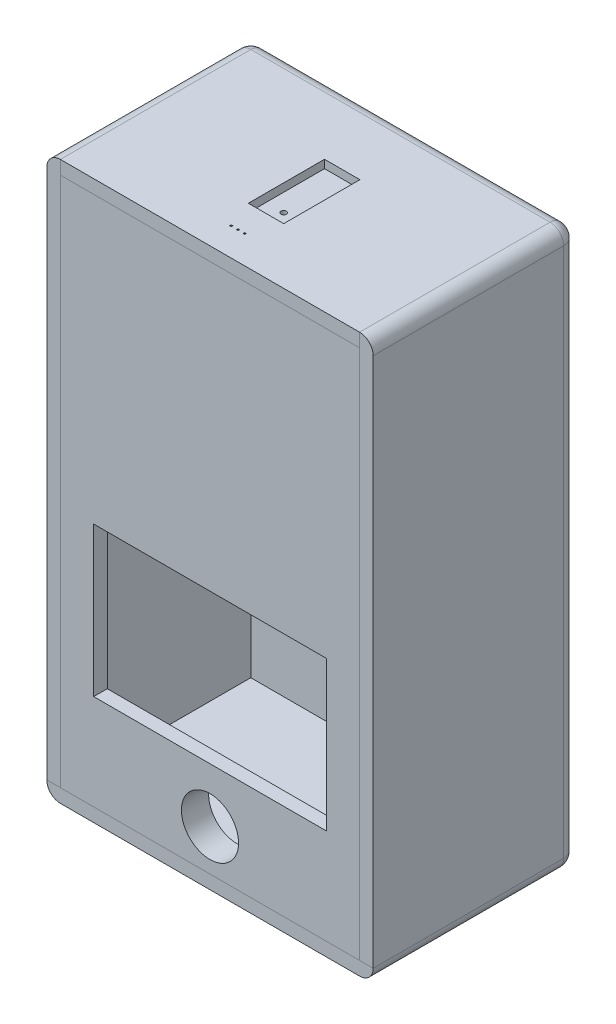
SolidWorks part; units mm, degrees
material "ABS"
ref_plane "Front Plane" through (0, 0, 0) normal (0, 0, 1) x (1, 0, 0)
ref_plane "Top Plane" through (0, 0, 0) normal (0, 1, 0) x (1, 0, 0)
ref_plane "Right Plane" through (0, 0, 0) normal (1, 0, 0) x (0, 0, -1)
sketch "Sketch5" plane through (0, 0, 0) normal (0, 1, 0) x (1, 0, 0)
  line L1 (0, 0) -> (-120, 0)
  line L2 (0, 0) -> (0, 75)
  line L3 (0, 75) -> (-120, 75)
  line L4 (-120, 0) -> (-120, 75)
  dimension "D1" = 75
  dimension "D2" = 120
extrude "Boss-Extrude4" add sketch "Sketch5" along normal blind 5
fillet "Fillet1" radius 5 2 edges at (0, 0, -37.5) (-120, 0, -37.5)
sketch "Sketch7" plane through (0, 5, 0) normal (0, 1, 0) x (1, 0, 0)
  line L0 (-120, 75) -> (-120, 0)
  line L1 (-120, 0) -> (-115, 0)
  line L2 (-120, 0) -> (0, 0) construction
  line L5 (-120, 75) -> (-115, 75)
  line L6 (0, 75) -> (-120, 75) construction
  line L7 (-115, 0) -> (-115, 75)
  line L8 (-60, 75) -> (-60, 0) construction
  line L9 (0, 0) -> (-5, 0)
  line L10 (-5, 0) -> (-5, 75)
  line L11 (0, 75) -> (-5, 75)
  line L12 (0, 75) -> (0, 0)
  point P11 (-60, 75)
  dimension "D1" = 5
  dimension "D2" = 5
  dimension "D3" = 60
extrude "Boss-Extrude7" add sketch "Sketch7" along normal blind 200 separate body
fillet "Fillet3" radius 5 1 edges at (-120, 205, -37.5)
sketch "Sketch8" plane through (0, 5, 0) normal (0, 1, 0) x (1, 0, 0)
  line L7 (-155, 70) -> (-115, 70) construction
  line L8 (-115, 0) -> (-115, 75) construction
  line L9 (-5, 75) -> (-5, 0) construction
  line L10 (-115, 70) -> (-5, 70)
  line L11 (-115, 70) -> (-115, 75)
  line L12 (-115, 75) -> (-5, 75)
  line L13 (-5, 70) -> (-5, 75)
  line L14 (0, 75) -> (-120, 75) construction
  point P0 (-155, 70)
  dimension "D1" = 110
  dimension "D2" = 5
extrude "Boss-Extrude8" add sketch "Sketch8" along normal blind 200 separate body
fillet "Fillet5" radius 5 1 edges at (0, 205, -37.5)
sketch "Sketch13" plane through (0, 0, 0) normal (0, 0, 1) x (1, 0, 0)
  line L1 (-115, 200) -> (-5, 200)
  line L2 (-115, 200) -> (-115, 205)
  line L3 (-115, 205) -> (-5, 205)
  line L4 (-5, 200) -> (-5, 205)
  point P0 (-115, 200)
extrude "Boss-Extrude9" add sketch "Sketch13" against normal up to next separate body
fillet "Fillet7" radius 5 2 edges at (-118.5355, 203.5355, -75) (-120, 102.5, -75)
fillet "Fillet8" radius 5 2 edges at (-1.4645, 203.5355, -75) (0, 102.5, -75)
fillet "Fillet9" radius 5 1 edges at (-60, 205, -75)
fillet "Fillet10" radius 5 3 edges at (-118.5355, 1.4645, -75) (-60, 0, -75) (-1.4645, 1.4645, -75)
sketch "Sketch14" plane through (0, 0, 0) normal (0, 0, 1) x (1, 0, 0)
  line L1 (-115, 200) -> (-5, 200)
  line L2 (-115, 200) -> (-115, 5)
  line L3 (-115, 5) -> (-5, 5)
  line L4 (-5, 200) -> (-5, 5)
extrude "Boss-Extrude10" add sketch "Sketch14" against normal blind 5 separate body
sketch "Sketch15" plane through (0, 0, 0) normal (0, 0, 1) x (1, 0, 0)
  line L0 (-60, 200) -> (-60, 5) construction
  line L1 (-5, 200) -> (-115, 200) construction
  line L2 (-120, 5) -> (0, 5) construction
  line L8 (-60, 115.06) -> (-115, 115.06) construction
  line L9 (-115, 205) -> (-115, 5) construction
  line L10 (-17.25, 95.06) -> (-17.25, 40.12)
  line L11 (-102.75, 95.06) -> (-17.25, 95.06)
  line L12 (-102.75, 40.12) -> (-102.75, 95.06)
  line L13 (-60, 40.12) -> (-102.75, 40.12)
  line L14 (-17.25, 40.12) -> (-60, 40.12)
  line L20 (-5, 205) -> (-5, 5) construction
  line L21 (-115, 200) -> (-115, 5) construction
  line L22 (-115, 5) -> (-5, 5) construction
  circle A0 centre (-60, 20.12) radius 10.5
  dimension "D8" = 15.12
  dimension "D2" = 20
  dimension "D7" = 21
  dimension "D3" = 12.25
  dimension "D4" = 12.25
  dimension "D5" = 35.12
  dimension "D6" = 85.5
  dimension "D19" = 35.12
extrude "Cut-Extrude8" cut sketch "Sketch15" against normal blind 5
sketch "Sketch16" plane through (0, 0, -5) normal (0, 0, -1) x (-1, 0, 0)
  circle A0 centre (60, 20.12) radius 10.5
  circle A1 centre (60, 20.12) radius 13.5
  dimension "D1" = 3
extrude "Boss-Extrude11" add sketch "Sketch16" along normal blind 5
sketch "Sketch17" plane through (0, 0, 0) normal (0, -1, 0) x (1, 0, 0)
  line L0 (-60, 0) -> (-60, -70) construction
  line L1 (-115, 0) -> (-5, 0) construction
  line L2 (-115, -70) -> (-5, -70) construction
  line L3 (-115, -35) -> (-5, -35) construction
  line L4 (-115, 0) -> (-115, -70) construction
  line L5 (-5, -70) -> (-5, 0) construction
  line L6 (-60, -60) -> (-19.224, -60) construction
  line L8 (-5, -75) -> (-115, -75) construction
  circle A0 centre (-70, -60) radius 5
  circle A1 centre (-50, -60) radius 5
  circle A3 centre (-25, -60) radius 5.776
  point P12 (-60, -60)
  point P13 (-70, -60)
  dimension "D3" = 10
  dimension "D4" = 10
  dimension "D5" = 15
  dimension "D6" = 11.5519
  dimension "D1" = 10
  dimension "D2" = 10
  dimension "D7" = 25
extrude "Cut-Extrude9" cut sketch "Sketch17" against normal blind 5
sketch "Sketch18" plane through (0, 205, 0) normal (0, 1, 0) x (1, 0, 0)
  line L0 (-60, 75) -> (-60, 0) construction
  line L1 (-5, 0) -> (-115, 0) construction
  line L2 (-60, 5) -> (-60, 10)
  line L3 (-60.3, 10) -> (-60, 10) construction
  line L4 (-60, 10) -> (-60.3, 10)
  line L5 (-60.3, 10) -> (-60.3, 10.6)
  line L6 (-60, 10) -> (-59.7, 10)
  line L7 (-60.3, 10.6) -> (-59.7, 10.6)
  line L8 (-59.7, 10.6) -> (-59.7, 10)
  line L9 (-61.25, 10.6) -> (-61.25, 10) construction
  line L10 (-58.75, 10.6) -> (-58.75, 10) construction
  line L11 (-62.5, 10) -> (-62.2, 10)
  line L12 (-62.2, 10) -> (-62.2, 10.6)
  line L13 (-62.2, 10.6) -> (-62.8, 10.6)
  line L14 (-62.8, 10.6) -> (-62.8, 10)
  line L15 (-62.5, 10) -> (-62.8, 10)
  line L16 (-57.5, 10) -> (-57.2, 10)
  line L17 (-57.2, 10) -> (-57.2, 10.6)
  line L18 (-57.2, 10.6) -> (-57.8, 10.6)
  line L19 (-57.8, 10.6) -> (-57.8, 10)
  line L20 (-57.5, 10) -> (-57.8, 10)
  line L21 (-60, 10.6) -> (-60, 14.4182) construction
  point P0 (-60, 5)
  dimension "D1" = 5
  dimension "D2" = 5
  dimension "D3" = 0.3
  dimension "D4" = 0.6
  dimension "D5" = 0.3
  dimension "D6" = 0.95
extrude "Cut-Extrude10" cut sketch "Sketch18" against normal up to next (5 mm away) contours L15 L11 L12 L13 L14 | L8 L7 L5 L4 L6 | L20 L16 L17 L18 L19 region at (-60, 205, -10.3) region at (-62.5, 205, -10.3) region at (-57.5, 205, -10.3)
sketch "Sketch19" plane through (0, 205, 0) normal (0, 1, 0) x (1, 0, 0)
  line L0 (-60, 10.6) -> (-60, 20.6) construction
  line L1 (-60.3, 10.6) -> (-59.7, 10.6) construction
  line L2 (-60, 20.6) -> (-66.5, 20.6)
  line L3 (-66.5, 20.6) -> (-66.5, 48.6)
  line L4 (-66.5, 48.6) -> (-60, 48.6)
  line L5 (-60, 48.6) -> (-53.5, 48.6)
  line L6 (-53.5, 48.6) -> (-53.5, 20.6)
  line L7 (-53.5, 20.6) -> (-60, 20.6)
  line L8 (-115, 70) -> (-115, 0) construction
  point P4 (-60, 48.6)
  point P5 (-66.5, 48.6)
  point P6 (-53.5, 48.6)
  dimension "D1" = 10
  dimension "D2" = 28
  dimension "D3" = 6.5
  dimension "D4" = 13
  dimension "D5" = 48.5
extrude "Cut-Extrude11" cut sketch "Sketch19" against normal blind 3
sketch "Sketch20" plane through (0, 202, 0) normal (0, 1, 0) x (1, 0, 0)
  line L0 (-60, 20.6) -> (-60, 27.1) construction
  line L1 (-66.5, 20.6) -> (-53.5, 20.6) construction
  line L2 (-60, 27.1) -> (-53.5, 27.1) construction
  line L3 (-53.5, 20.6) -> (-53.5, 48.6) construction
  circle A0 centre (-60, 27.1) radius 1
  dimension "D3" = 2
  dimension "D1" = 6.5
  dimension "D2" = 6.5
extrude "Cut-Extrude12" cut sketch "Sketch20" against normal up to next (2 mm away)
